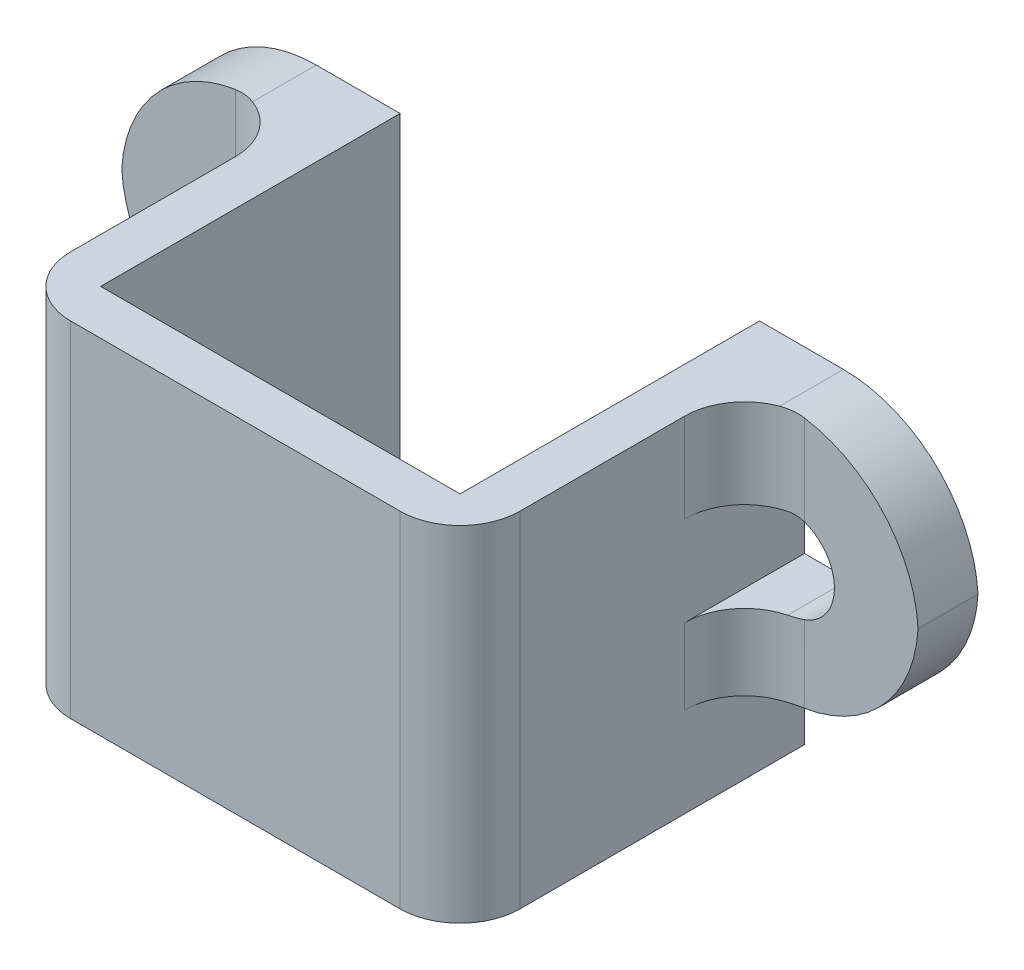
SolidWorks part; units mm, degrees
note: The reader was unsure of these and kept them because the rebuilt part matched: shared geometry of "Szkic1<7>", "Szkic1<8>".
material "ABS"
ref_plane "Płaszczyzna przednia" through (0, 0, 0) normal (0, 0, 1) x (1, 0, 0)
ref_plane "Płaszczyzna górna" through (0, 0, 0) normal (0, 1, 0) x (1, 0, 0)
ref_plane "Płaszczyzna prawa" through (0, 0, 0) normal (1, 0, 0) x (0, 0, -1)
sketch "Szkic1" plane through (0, 0, 0) normal (0, 0, 1) x (1, 0, 0)
  line L0 (6.638, -4.5126) -> (12.438, -4.5126)
  line L1 (-8.362, 3.9874) -> (6.638, 3.9874)
  line L2 (-8.362, 3.9874) -> (-8.362, -7.5126)
  line L3 (-8.362, -7.5126) -> (6.638, -7.5126)
  line L4 (6.638, 3.9874) -> (6.638, -7.5126)
  line L5 (-8.362, 3.9874) -> (-14.162, 3.9874)
  line L6 (-8.362, 3.9874) -> (-8.362, -7.5126)
  line L7 (-8.362, -7.5126) -> (-14.162, -7.5126)
  line L8 (-14.162, 3.9874) -> (-14.162, -7.5126)
  line L9 (6.638, 3.9874) -> (12.438, 3.9874)
  line L10 (6.638, 3.9874) -> (6.638, -7.5126)
  line L11 (6.638, -7.5126) -> (12.438, -7.5126)
  line L12 (12.438, 3.9874) -> (12.438, -7.5126)
  line L13 (-8.362, -7.5126) -> (-6.862, -7.5126)
  line L14 (-8.362, -7.5126) -> (-8.362, 3.9874)
  line L15 (-8.362, 3.9874) -> (-6.862, 3.9874)
  line L16 (-6.862, -7.5126) -> (-6.862, 3.9874)
  line L17 (6.638, -7.5126) -> (5.138, -7.5126)
  line L18 (6.638, -7.5126) -> (6.638, 3.9874)
  line L19 (6.638, 3.9874) -> (5.138, 3.9874)
  line L20 (5.138, -7.5126) -> (5.138, 3.9874)
  line L21 (-14.162, 3.9874) -> (-8.362, 3.9874)
  line L22 (-14.162, 3.9874) -> (-14.162, -4.5126)
  line L23 (-14.162, -4.5126) -> (-8.362, -4.5126)
  line L24 (-8.362, 3.9874) -> (-8.362, -4.5126)
  line L25 (-9.862, -1.9859) -> (-8.362, -1.9859)
  line L26 (-9.862, 1.0141) -> (-8.362, 1.0141)
  line L27 (8.138, -1.9859) -> (6.638, -1.9859)
  line L28 (6.638, -1.9859) -> (6.638, 1.0141)
  line L29 (6.638, 1.0141) -> (8.138, 1.0141)
  circle A0 centre (-9.862, -0.4859) radius 1.5
  circle A1 centre (8.138, -0.4859) radius 1.5
  dimension "D9" = 3
  dimension "D10" = 3
  dimension "D1" = 11.5
  dimension "D2" = 15
  dimension "D3" = 5.8
  dimension "D4" = 5.8
  dimension "D5" = 12
  dimension "D6" = 1.5
  dimension "D7" = 8.5
  dimension "D8" = 18
extrude "Dodanie-wyciągnięcie4" add sketch "Szkic1" along normal blind 2 contours L5 L8 L7 L2 | L12 L9 L4 L11
extrude "Dodanie-wyciągnięcie5" add sketch "Szkic1<7>" along normal blind 11.5 contours L3 L16 L1 L2 | L3 L20 L1 L16 | L20 L3 L4 L1
sketch "Szkic1<7>" plane through (0, 0, 0) normal (0, 0, 1) x (1, 0, 0) same geometry as "Szkic1"
extrude "Wytnij-wyciągnięcie1" cut sketch "Szkic1<8>" along normal blind 10 contours L3 L20 L1 L16
sketch "Szkic1<8>" plane through (0, 0, 0) normal (0, 0, 1) x (1, 0, 0) same geometry as "Szkic1"
fillet "Zaokrąglenie1" radius 4.5 2 edges at (-14.162, 3.9874, 1) (-14.162, -4.5126, 1)
fillet "Zaokrąglenie2" radius 4.5 2 edges at (12.438, -4.5126, 1) (12.438, 3.9874, 1)
fillet "Zaokrąglenie3" radius 2 1 edges at (6.638, 2.5008, 2)
fillet "Zaokrąglenie4" radius 2 5 edges at (-8.362, 2.5008, 2) (-8.362, -3.2492, 2) (-8.362, -1.7626, 11.5) (6.638, -1.7626, 11.5) (6.638, -3.2492, 2)
